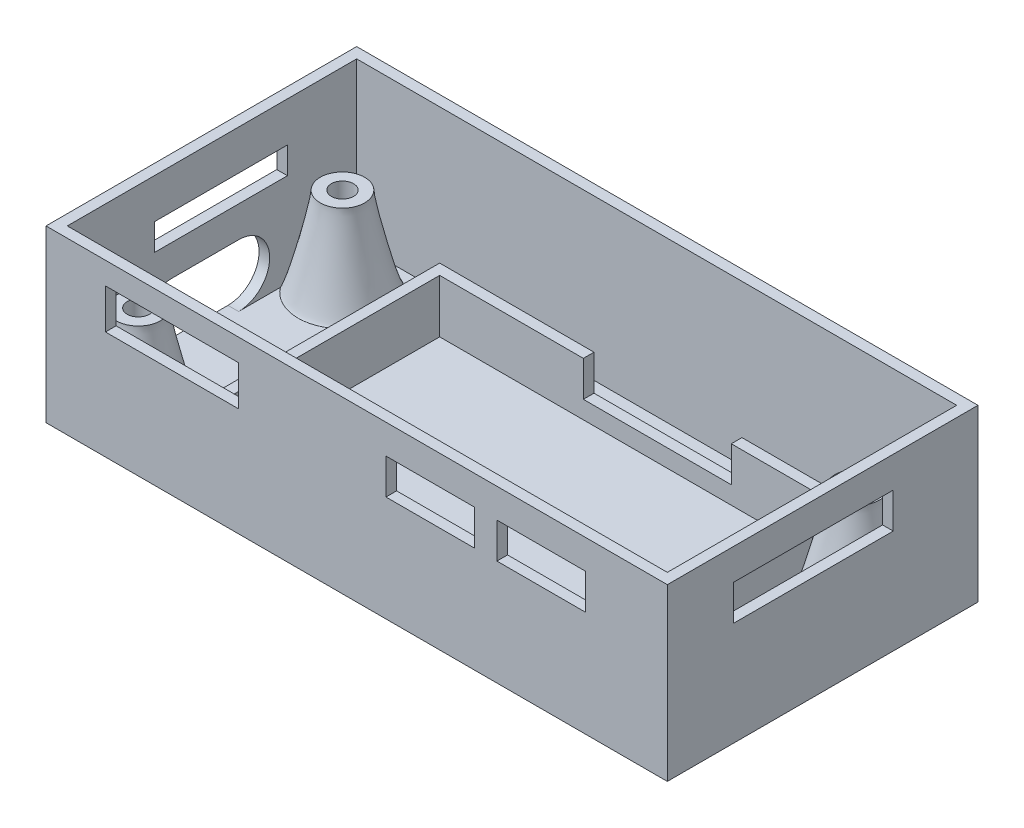
SolidWorks part; units mm, degrees
ref_plane "Front" through (0, 0, 0) normal (0, 0, 1) x (1, 0, 0)
ref_plane "Top" through (0, 0, 0) normal (0, 1, 0) x (1, 0, 0)
ref_plane "Right" through (0, 0, 0) normal (1, 0, 0) x (0, 0, -1)
sketch "Sketch1" plane through (0, 0, 0) normal (0, 1, 0) x (1, 0, 0)
  line L1 (0, 0) -> (70, 0)
  line L2 (0, 0) -> (0, -35)
  line L3 (0, -35) -> (70, -35)
  line L4 (70, 0) -> (70, -35)
  dimension "D1" = 35
  dimension "D2" = 70
extrude "Boss-Extrude1" add sketch "Sketch1" along normal blind 1.2
sketch "Sketch2" plane through (0, 1.2, 0) normal (0, 1, 0) x (1, 0, 0)
  line L0 (0, -35) -> (70, -35) construction
  line L1 (0, -35) -> (70, -35)
  line L2 (0, -35) -> (0, 0)
  line L3 (0, 0) -> (70, 0)
  line L4 (70, -35) -> (70, 0)
  line L5 (1.2, -33.8) -> (1.2, -1.2)
  line L6 (1.2, -1.2) -> (68.8, -1.2)
  line L7 (68.8, -33.8) -> (68.8, -1.2)
  line L8 (1.2, -33.8) -> (68.8, -33.8)
  dimension "D1" = 1.2
extrude "Boss-Extrude2" add sketch "Sketch2" along normal blind 18
sketch "Sketch3" plane through (0, 1.2, 0) normal (0, 1, 0) x (1, 0, 0)
  line L0 (1.2, -1.2) -> (1.2, -33.8) construction
  line L1 (1.2, -33.8) -> (68.8, -33.8) construction
  circle A0 centre (5.2, -29.8) radius 2.5
  circle A1 centre (63.2, -29.8) radius 2.5
  circle A2 centre (63.2, -6.8) radius 2.5
  circle A3 centre (5.2, -6.8) radius 2.5
  dimension "D1" = 5
  dimension "D4" = 2
  dimension "D2" = 4
  dimension "D3" = 4
  dimension "D5" = 2
extrude "Boss-Extrude3" add sketch "Sketch3" along normal blind 10
sketch "Sketch4" plane through (0, 11.2, 0) normal (0, 1, 0) x (1, 0, 0)
  circle A0 centre (5.2, -29.8) radius 1.25
  circle A1 centre (5.2, -6.8) radius 1.25
  circle A2 centre (63.2, -6.8) radius 1.25
  circle A3 centre (63.2, -29.8) radius 1.25
  dimension "D1" = 2.5
  dimension "D2" = 2.5
  dimension "D3" = 2.5
  dimension "D4" = 2.5
extrude "Cut-Extrude1" cut sketch "Sketch4" against normal through all
sketch "Sketch5" plane through (0, 0, 0) normal (-1, 0, 0) x (0, 0, 1)
  line L0 (0, 0) -> (35, 0) construction
  line L1 (9, 14.7) -> (24, 14.7)
  line L2 (9, 14.7) -> (9, 11.7)
  line L3 (9, 11.7) -> (24, 11.7)
  line L4 (24, 14.7) -> (24, 11.7)
  line L5 (35, 19.2) -> (35, 0) construction
  dimension "D1" = 3
  dimension "D2" = 15
  dimension "D3" = 11.7
  dimension "D4" = 11
extrude "Cut-Extrude2" cut sketch "Sketch5" against normal blind 2
sketch "Sketch7" plane through (0, 0, 33.8) normal (0, 0, -1) x (-1, 0, 0)
  line L0 (-68.8, 19.2) -> (-68.8, 1.2) construction
  line L1 (-50.8, 15.9) -> (-60.8, 15.9)
  line L2 (-50.8, 15.9) -> (-50.8, 11.9)
  line L3 (-50.8, 11.9) -> (-60.8, 11.9)
  line L4 (-60.8, 15.9) -> (-60.8, 11.9)
  line L5 (-38.3, 15.9) -> (-48.3, 15.9)
  line L6 (-38.3, 15.9) -> (-38.3, 11.9)
  line L7 (-38.3, 11.9) -> (-48.3, 11.9)
  line L8 (-48.3, 15.9) -> (-48.3, 11.9)
  line L9 (-1.2, 1.2) -> (-68.8, 1.2) construction
  dimension "D1" = 10
  dimension "D2" = 10
  dimension "D3" = 4
  dimension "D4" = 4
  dimension "D5" = 8
  dimension "D6" = 20.5
  dimension "D7" = 10.7
  dimension "D8" = 10.7
extrude "Cut-Extrude3" cut sketch "Sketch7" against normal blind 2
sketch "Sketch8" plane through (0, 0, 33.8) normal (0, 0, -1) x (-1, 0, 0)
  line L0 (-1.2, 1.2) -> (-68.8, 1.2) construction
  line L1 (-6.7, 16.7) -> (-21.7, 16.7)
  line L2 (-6.7, 16.7) -> (-6.7, 12.2)
  line L3 (-6.7, 12.2) -> (-21.7, 12.2)
  line L4 (-21.7, 16.7) -> (-21.7, 12.2)
  line L5 (-1.2, 19.2) -> (-1.2, 1.2) construction
  dimension "D1" = 15
  dimension "D2" = 4.5
  dimension "D3" = 11
  dimension "D4" = 5.5
extrude "Cut-Extrude4" cut sketch "Sketch8" against normal blind 2
sketch "Sketch9" plane through (68.8, 0, 0) normal (-1, 0, 0) x (0, 0, 1)
  line L0 (33.8, 1.2) -> (1.2, 1.2) construction
  line L1 (9.55, 15.7) -> (27.55, 15.7)
  line L2 (9.55, 15.7) -> (9.55, 11.7)
  line L3 (9.55, 11.7) -> (27.55, 11.7)
  line L4 (27.55, 15.7) -> (27.55, 11.7)
  line L5 (33.8, 19.2) -> (33.8, 1.2) construction
  dimension "D1" = 18
  dimension "D2" = 4
  dimension "D3" = 10.5
  dimension "D4" = 6.25
extrude "Cut-Extrude5" cut sketch "Sketch9" against normal blind 2
fillet "Fillet1" radius 2.5 4 edges at (63.2, 1.2, 32.3) (5.2, 1.2, 32.3) (63.2, 1.2, 9.3) (5.2, 1.2, 9.3) second distance 10 conic rho 0.1 first distance on face at (5.2, 1.2, 9.3)
sketch "Sketch15" plane through (1.2, 0, 0) normal (1, 0, 0) x (0, 0, -1)
  line L0 (-9.7996, 1.2) -> (-26.8004, 1.2) construction
  line L1 (-1.2, 19.2) -> (-1.2, 1.2) construction
  circle A0 centre (-14.5, 4.7) radius 3.5
  circle A1 centre (-22, 4.7) radius 3.5
  dimension "D1" = 7
  dimension "D2" = 3.5
  dimension "D3" = 13.3
  dimension "D4" = 2
extrude "Cut-Extrude7" cut sketch "Sketch15" against normal blind 2
sketch "Sketch17" plane through (0, 1.2, 0) normal (0, 1, 0) x (1, 0, 0)
  line L0 (68.8, -33.8) -> (68.8, -1.2) construction
  line L1 (15, -5.65) -> (57.8, -5.65)
  line L2 (15, -5.65) -> (15, -29.35)
  line L3 (15, -29.35) -> (57.8, -29.35)
  line L4 (57.8, -5.65) -> (57.8, -29.35)
  line L15 (13.8, -4.45) -> (59, -4.45)
  line L16 (59, -4.45) -> (59, -30.55)
  line L17 (13.8, -30.55) -> (59, -30.55)
  line L18 (13.8, -4.45) -> (13.8, -30.55)
  point P4 (57.8, -17.5)
  point P7 (68.8, -17.5)
  dimension "D1" = 23.7
  dimension "D2" = 42.8
  dimension "D3" = 0
  dimension "D4" = 11
  dimension "D5" = 1.2
extrude "Boss-Extrude4" add sketch "Sketch17" along normal blind 6
sketch "Sketch18" plane through (0, 0, 0) normal (-1, 0, 0) x (0, 0, 1)
  line L1 (14.5, 8.2) -> (22, 8.2)
  line L2 (14.5, 8.2) -> (14.5, 1.2)
  line L3 (14.5, 1.2) -> (22, 1.2)
  line L4 (22, 8.2) -> (22, 1.2)
  circle A0 centre (14.5, 4.7) radius 3.5 construction
  circle A1 centre (22, 4.7) radius 3.5 construction
extrude "Cut-Extrude8" cut sketch "Sketch18" against normal blind 2
sketch "Sketch19" plane through (0, 7.2, 0) normal (0, 1, 0) x (1, 0, 0)
  line L1 (31.1878, -3.2949) -> (47.8568, -3.2949)
  line L2 (31.1878, -3.2949) -> (31.1878, -31.4397)
  line L3 (31.1878, -31.4397) -> (47.8568, -31.4397)
  line L4 (47.8568, -3.2949) -> (47.8568, -31.4397)
extrude "Cut-Extrude9" cut sketch "Sketch19" against normal blind 4
